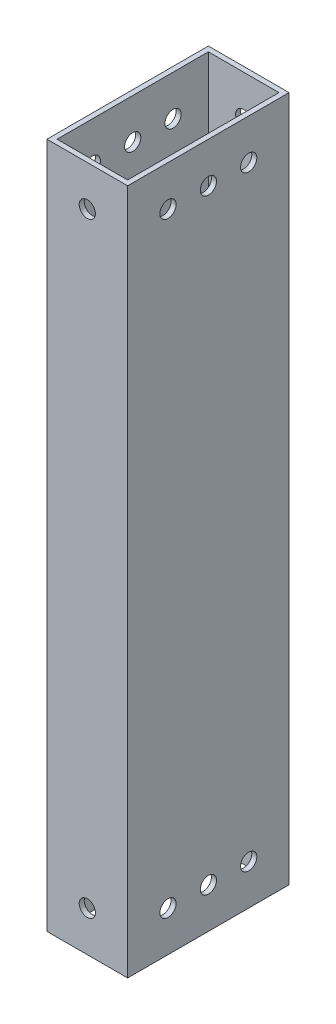
SolidWorks part; units mm, degrees
material "6061-T6 (SS)"
ref_plane "Front" through (0, 0, 0) normal (0, 0, 1) x (1, 0, 0)
ref_plane "Top" through (0, 0, 0) normal (0, 1, 0) x (1, 0, 0)
ref_plane "Right" through (0, 0, 0) normal (1, 0, 0) x (0, 0, -1)
sketch "Sketch1" plane through (0, 0, 0) normal (0, 1, 0) x (1, 0, 0)
  line L1 (12.7, 25.4) -> (-12.7, 25.4)
  line L2 (12.7, 25.4) -> (12.7, -25.4)
  line L3 (12.7, -25.4) -> (-12.7, -25.4)
  line L4 (-12.7, 25.4) -> (-12.7, -25.4)
  line L5 (12.7, 25.4) -> (-12.7, -25.4) construction
  line L6 (12.7, -25.4) -> (-12.7, 25.4) construction
  point P0 (0, 0)
  dimension "D1" = 25.4
  dimension "D2" = 50.8
extrude "Extrude-Thin1" add sketch "Sketch1" along normal up to surface (215.9 mm away) thin thin type one direction reverse wall 1.5875
sketch "Sketch4" plane through (-12.7, 0, 0) normal (-1, 0, 0) x (0, 0, 1)
  line L0 (-12.7, 12.7) -> (12.7, 12.7) construction
  line L3 (-12.7, 203.2) -> (12.7, 203.2) construction
  line L4 (-25.4, 0) -> (25.4, 0) construction
  line L5 (-25.4, 215.9) -> (25.4, 215.9) construction
  point P1 (-12.7, 12.7)
  point P2 (12.7, 12.7)
  point P6 (-12.7, 203.2)
  point P7 (12.7, 203.2)
  point P11 (0, 203.2)
  point P17 (0, 12.7)
  point P27 (-12.7, 203.2)
  point P29 (12.7, 203.2)
  point P31 (-12.7, 12.7)
  point P33 (12.7, 12.7)
  dimension "D1" = 12.7
  dimension "D2" = 12.7
  dimension "D3" = 12.7
hole_wizard "#10 Clearance Hole1" positions "Sketch4" profile "Sketch3" hole size "#10" standard "ANSI Inch" end condition through all
sketch "Sketch3" plane through (-12.7, 12.7, 12.7) normal (0, 1, 0) x (0, 0, 1)
  line L0 (0, 0) -> (0, 25.4)
  line L1 (0, 25.4) -> (2.5527, 25.4)
  line L2 (2.5527, 25.4) -> (2.5527, 0)
  line L5 (2.5527, 0) -> (0, 0)
  line L11 (0, -6.35) -> (0, 107.95) construction
  dimension "Thru Hole Dia." = 5.1054
  dimension "Thru Hole Depth" = 25.4
sketch "Sketch7" plane through (0, 0, 25.4) normal (0, 0, 1) x (1, 0, 0)
  line L0 (-12.7, 0) -> (12.7, 0) construction
  line L1 (-12.7, 215.9) -> (12.7, 215.9) construction
  point P0 (0, 203.2)
  point P2 (0, 12.7)
  dimension "D1" = 12.7
  dimension "D2" = 12.7
hole_wizard "#10 Clearance Hole2" positions "Sketch7" profile "Sketch6" hole size "#10" standard "ANSI Inch" end condition through all
sketch "Sketch6" plane through (0, 203.2, 25.4) normal (1, 0, 0) x (0, -1, 0)
  line L0 (0, 0) -> (0, 50.8)
  line L1 (0, 50.8) -> (2.5527, 50.8)
  line L2 (2.5527, 50.8) -> (2.5527, 0)
  line L5 (2.5527, 0) -> (0, 0)
  line L11 (0, -6.35) -> (0, 107.95) construction
  dimension "Thru Hole Dia." = 5.1054
  dimension "Thru Hole Depth" = 50.8
